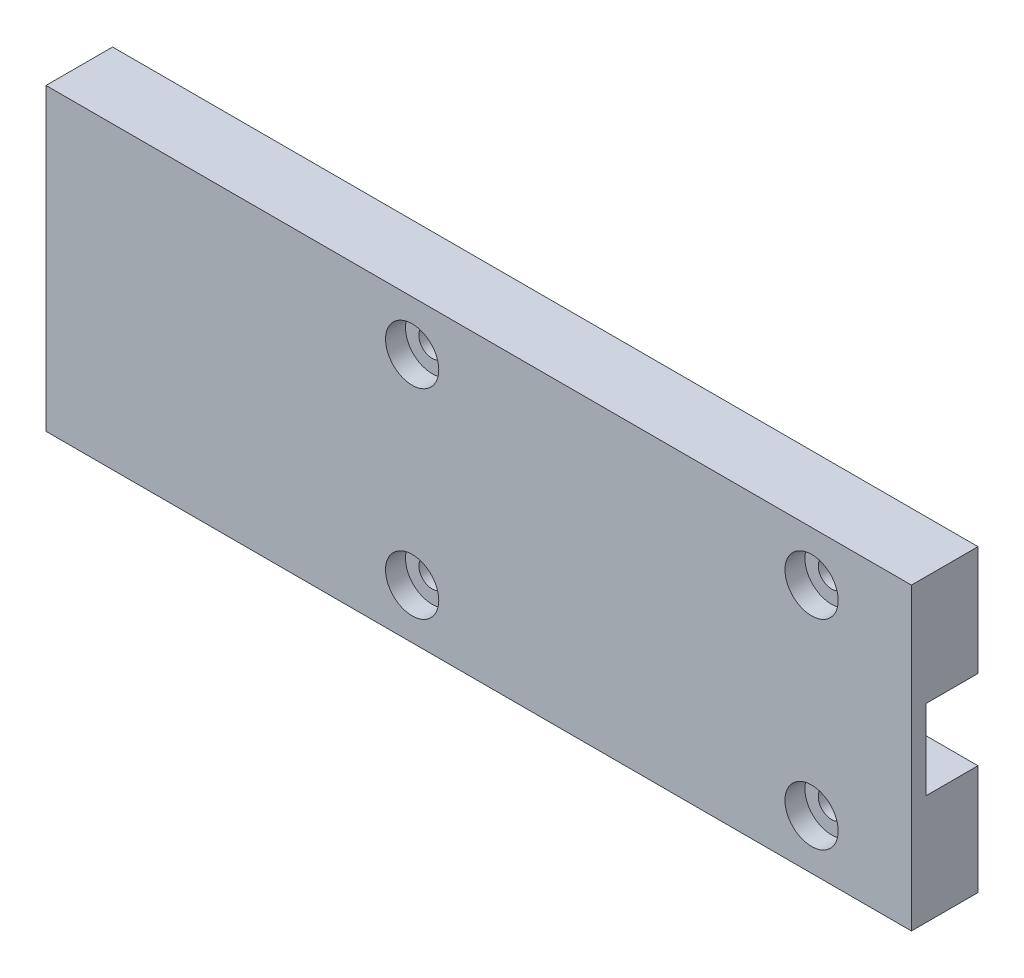
SolidWorks part; units mm, degrees
ref_plane "Front Plane" through (0, 0, 0) normal (0, 0, 1) x (1, 0, 0)
ref_plane "Top Plane" through (0, 0, 0) normal (0, 1, 0) x (1, 0, 0)
ref_plane "Right Plane" through (0, 0, 0) normal (1, 0, 0) x (0, 0, -1)
sketch "Sketch1" plane through (0, 0, 0) normal (0, 0, 1) x (1, 0, 0)
  line L0 (130, 45) -> (130, 0) construction
  line L1 (0, 0) -> (130, 0)
  line L2 (0, 0) -> (0, 45)
  line L3 (0, 45) -> (130, 45)
  line L4 (130, 0) -> (130, 45)
  line L5 (0, 0) -> (130, 45) construction
  line L6 (0, 45) -> (130, 0) construction
  line L7 (0, 45) -> (130, 45) construction
  point P4 (65, 22.5)
extrude "Boss-Extrude1" add sketch "Sketch1" along normal blind 10
sketch "Sketch2" plane through (0, 0, 0) normal (0, 0, -1) x (-1, 0, 0)
  line L0 (-130, 0) -> (-130, 45) construction
  line L1 (-130, 16.5) -> (-20, 16.5)
  line L2 (-130, 16.5) -> (-130, 28.5)
  line L3 (-130, 28.5) -> (-20, 28.5)
  line L4 (-20, 16.5) -> (-20, 28.5)
  line L5 (-130, 16.5) -> (-20, 28.5) construction
  line L6 (-130, 28.5) -> (-20, 16.5) construction
  line L7 (-130, 45) -> (0, 45) construction
  line L8 (0, 0) -> (-130, 0) construction
  point P4 (-75, 22.5)
  dimension "D1" = 16.5
  dimension "D2" = 16.5
  dimension "D3" = 110
extrude "Cut-Extrude1" cut sketch "Sketch2" against normal blind 7.8
sketch "Sketch4" plane through (0, 0, 10) normal (0, 0, 1) x (1, 0, 0)
  line L0 (130, 0) -> (130, 45) construction
  line L1 (115, 7.5) -> (55, 7.5) construction
  line L2 (115, 7.5) -> (115, 37.5) construction
  line L3 (115, 37.5) -> (55, 37.5) construction
  line L4 (55, 7.5) -> (55, 37.5) construction
  line L5 (115, 7.5) -> (55, 37.5) construction
  line L6 (115, 37.5) -> (55, 7.5) construction
  line L7 (130, 22.5) -> (0, 22.5) construction
  line L8 (0, 45) -> (0, 0) construction
  circle A0 centre (55, 37.5) radius 2
  circle A1 centre (115, 37.5) radius 2
  circle A2 centre (115, 7.5) radius 2
  circle A3 centre (55, 7.5) radius 2
  point P0 (85, 22.5)
  dimension "D4" = 4
  dimension "D1" = 30
  dimension "D2" = 60
  dimension "D3" = 15
extrude "Cut-Extrude3" cut sketch "Sketch4" against normal through all
sketch "Sketch5" plane through (0, 0, 10) normal (0, 0, 1) x (1, 0, 0)
  circle A0 centre (55, 37.5) radius 4
  circle A1 centre (115, 37.5) radius 4
  circle A2 centre (115, 7.5) radius 4
  circle A3 centre (55, 7.5) radius 4
  dimension "D1" = 8
extrude "Cut-Extrude4" cut sketch "Sketch5" against normal blind 3
sketch "Sketch6" plane through (0, 0, 0) normal (0, 0, -1) x (-1, 0, 0)
  line L1 (-4.5, 43) -> (-45.5, 43)
  line L2 (-4.5, 43) -> (-4.5, 2)
  line L3 (-4.5, 2) -> (-45.5, 2)
  line L4 (-45.5, 43) -> (-45.5, 2)
  line L5 (-4.5, 43) -> (-45.5, 2) construction
  line L6 (-4.5, 2) -> (-45.5, 43) construction
  point P4 (-25, 22.5)
extrude "Cut-Extrude5" cut sketch "Sketch6" against normal up to surface (7.8 mm away) up to face at (75, 22.5, 7.8)
